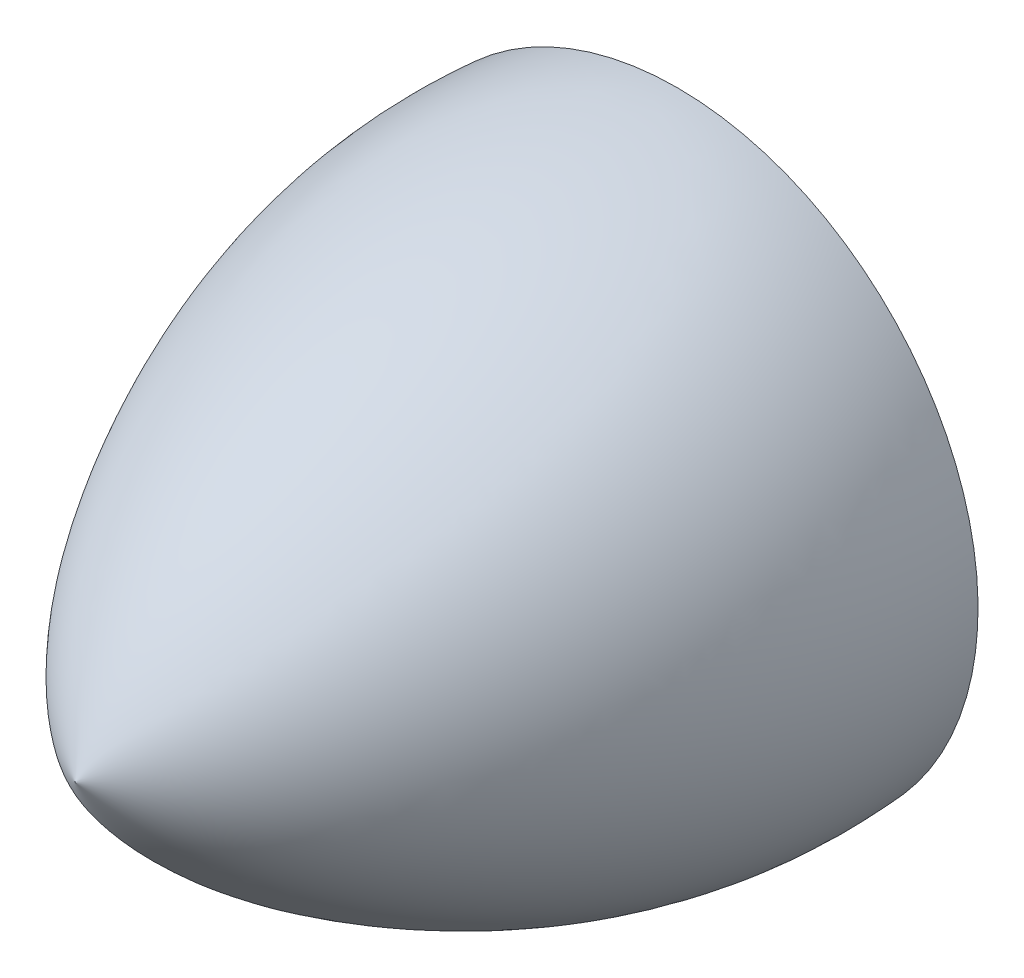
SolidWorks part; units mm, degrees
ref_plane "Front Plane" through (0, 0, 0) normal (0, 0, 1) x (1, 0, 0)
ref_plane "Top Plane" through (0, 0, 0) normal (0, 1, 0) x (1, 0, 0)
ref_plane "Right Plane" through (0, 0, 0) normal (1, 0, 0) x (0, 0, -1)
sketch "Sketch1" plane through (0, 0, 0) normal (1, 0, 0) x (0, 0, -1)
  line L0 (0, -35) -> (0, 35)
  line L1 (0, 0) -> (-70.104, 0) construction
  line L2 (0, -35) -> (-70.104, 0)
  spline S0 degree 3 poles (-70.104, 0) (-64.6188, 11.1696) (-42.348, 28.8049) (-15.522, 36.223) (0, 35) knots 0 0 0 0 0.44611 1 1 1 1
  point P3 (-62.8884, 10.5387)
  point P4 (0, 0)
  point P7 (-43.8418, 24.8708)
  point P8 (-25.361, 32.414)
  dimension "D1" = 70
  dimension "D2" = 70.104
revolve "Revolve1" add sketch "Sketch1" angle 360 about L1 region at (0, 14.6722, 27.946)
